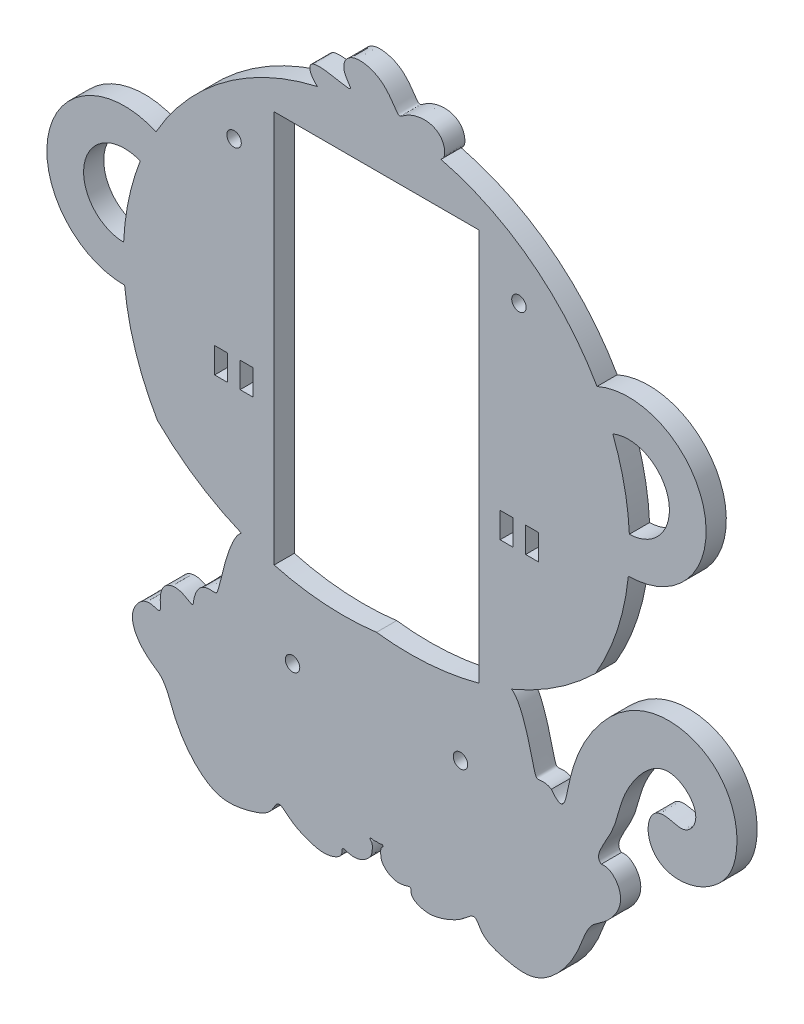
SolidWorks part; units mm, degrees
ref_plane "Front Plane" through (0, 0, 0) normal (0, 0, 1) x (1, 0, 0)
ref_plane "Top Plane" through (0, 0, 0) normal (0, 1, 0) x (1, 0, 0)
ref_plane "Right Plane" through (0, 0, 0) normal (1, 0, 0) x (0, 0, -1)
sketch "Model" plane through (0, 0, 0) normal (0, 0, 1) x (1, 0, 0)
  line L0 (-354.7776, 349.4226) -> (-354.7776, 392.0292) construction
  line L1 (-368.5276, 390.0292) -> (-368.5276, 362.0292)
  line L2 (-368.5276, 390.0292) -> (-341.0276, 390.0292)
  line L21 (-354.7776, 390.0292) -> (-354.7776, 362.0292)
  line L26 (-368.5276, 362.0292) -> (-341.0276, 362.0292)
  line L27 (-341.0276, 390.0292) -> (-341.0276, 362.0292)
  line L28 (-354.7776, 390.0292) -> (-354.7776, 497.7106) construction
  line L29 (-368.5276, 390.0292) -> (-378.8528, 390.0292)
  line L31 (-368.5276, 486.0185) -> (-378.8528, 486.0185)
  line L32 (-378.8528, 390.0292) -> (-378.8528, 486.0185)
  line L33 (-378.8528, 412.6938) -> (-394.4933, 412.6938)
  line L34 (-378.8528, 412.6938) -> (-378.8528, 468.4071)
  line L35 (-378.8528, 468.4071) -> (-394.4933, 468.4071)
  line L36 (-394.4933, 412.6938) -> (-394.4933, 468.4071)
  line L37 (-354.7776, 390.0292) -> (-368.5276, 390.0292)
  line L38 (-354.7776, 390.0292) -> (-354.7776, 486.0185)
  line L39 (-354.7776, 486.0185) -> (-368.5276, 486.0185)
  line L41 (-354.7776, 486.0185) -> (-341.0276, 486.0185)
  line L42 (-341.0276, 486.0185) -> (-330.7024, 486.0185)
  line L43 (-341.0276, 390.0292) -> (-330.7024, 390.0292)
  line L44 (-330.7024, 412.6938) -> (-315.0619, 412.6938)
  line L45 (-315.0619, 412.6938) -> (-315.0619, 468.4071)
  line L46 (-330.7024, 468.4071) -> (-315.0619, 468.4071)
  line L47 (-330.7024, 390.0292) -> (-330.7024, 486.0185)
  line L56 (-325.7024, 431.4116) -> (-322.7024, 431.4116)
  line L57 (-325.7024, 431.4116) -> (-325.7024, 425.4116)
  line L58 (-325.7024, 425.4116) -> (-322.7024, 425.4116)
  line L59 (-322.7024, 431.4116) -> (-322.7024, 425.4116)
  line L61 (-319.7024, 431.4116) -> (-316.7024, 431.4116)
  line L62 (-319.7024, 431.4116) -> (-319.7024, 425.4116)
  line L63 (-319.7024, 425.4116) -> (-316.7024, 425.4116)
  line L64 (-316.7024, 431.4116) -> (-316.7024, 425.4116)
  line L65 (-389.8528, 425.4116) -> (-392.8528, 425.4116)
  line L66 (-392.8528, 431.4116) -> (-392.8528, 425.4116)
  line L67 (-389.8528, 431.4116) -> (-392.8528, 431.4116)
  line L68 (-389.8528, 431.4116) -> (-389.8528, 425.4116)
  line L69 (-383.8528, 425.4116) -> (-386.8528, 425.4116)
  line L70 (-386.8528, 431.4116) -> (-386.8528, 425.4116)
  line L71 (-383.8528, 431.4116) -> (-386.8528, 431.4116)
  line L72 (-383.8528, 431.4116) -> (-383.8528, 425.4116)
  line L75 (-341.0276, 486.0185) -> (-354.7776, 486.0185)
  circle A0 centre (-295.506, 451.3512) radius 18.2563
  circle A1 centre (-295.506, 451.3512) radius 9.6191
  circle A2 centre (-414.0491, 451.3512) radius 9.6191
  circle A3 centre (-414.0491, 451.3512) radius 18.2562
  arc A4 (-354.7776, 392.0292) -> (-303.2483, 409.4214) centre (-346.9752, 453.9435) ccw
  arc A5 (-303.2483, 409.4214) -> (-354.7776, 497.7106) centre (-353.9365, 439.0196) ccw
  arc A6 (-354.7776, 497.7106) -> (-406.3069, 409.4214) centre (-355.6187, 439.0196) ccw
  arc A7 (-406.3069, 409.4214) -> (-354.7776, 392.0292) centre (-362.58, 453.9435) ccw
  circle A8 centre (-388.2776, 475.7792) radius 1.7 construction
  circle A9 centre (-321.2776, 475.7792) radius 1.7 construction
  circle A10 centre (-388.2776, 475.7792) radius 1.7
  circle A11 centre (-321.2776, 475.7792) radius 1.7
  circle A12 centre (-374.5276, 375.7792) radius 1.7 construction
  circle A13 centre (-335.0276, 375.7792) radius 1.7 construction
  circle A14 centre (-374.5276, 375.7792) radius 1.7
  circle A15 centre (-335.0276, 375.7792) radius 1.7
  spline S0 degree 5 poles (-386.5513, 396.3273) (-386.9161, 396.0792) (-387.366, 395.6344) (-387.8968, 394.8986) (-388.5033, 393.7572) (-389.1715, 392.131) (-389.5779, 391.0147) (-389.9703, 389.8193) (-390.4193, 388.3234) (-390.8333, 386.8049) (-391.2016, 385.3464) (-391.5167, 384.0353) (-391.7817, 382.9443) (-391.9754, 382.2094) (-392.154, 381.6648) (-392.3367, 381.3111) (-392.5515, 381.1299) (-392.8335, 381.0822) (-393.2115, 381.1155) (-393.6934, 381.1695) (-394.2612, 381.1826) (-394.881, 381.0994) (-395.5104, 380.8776) (-396.1059, 380.4945) (-396.6315, 379.9559) (-397.064, 379.2975) (-397.3921, 378.574) (-397.6173, 377.8496) (-397.7535, 377.1888) (-397.8274, 376.647) (-397.8791, 376.2603) (-397.9596, 376.0385) (-398.1148, 375.9725) (-398.366, 376.0408) (-398.7069, 376.2147) (-399.1201, 376.4601) (-399.5915, 376.7412) (-400.118, 377.0223) (-400.6998, 377.2689) (-401.4638, 377.484) (-402.3002, 377.5538) (-403.1741, 377.4267) (-404.0022, 377.0659) (-404.6982, 376.4644) (-405.1535, 375.8118) (-405.4613, 375.0322) (-405.6199, 374.1669) (-405.658, 373.2789) (-405.6265, 372.4425) (-405.5875, 371.7311) (-405.6037, 371.2053) (-405.7274, 370.9008) (-405.9901, 370.8167) (-406.3911, 370.9021) (-406.9056, 371.0748) (-407.4962, 371.2433) (-408.1222, 371.3275) (-408.7511, 371.2827) (-409.3596, 371.0975) (-409.9312, 370.7828) (-410.4544, 370.3635) (-410.9212, 369.8697) (-411.3251, 369.3269) (-411.6596, 368.7503) (-411.9191, 368.1478) (-412.0987, 367.5224) (-412.1944, 366.8744) (-412.2033, 366.204) (-412.0922, 365.2374) (-411.7958, 364.2405) (-411.2536, 363.0979) (-410.5055, 362.004) (-409.6286, 361.0209) (-408.9407, 360.363) (-408.2617, 359.7955) (-407.7193, 359.3836) (-407.2138, 359.0282) (-406.7532, 358.7179) (-406.3372, 358.4326) (-405.9584, 358.1461) (-405.6064, 357.8322) (-405.2709, 357.469) (-404.9452, 357.0452) (-404.6288, 356.5637) (-404.3252, 356.0366) (-404.0394, 355.4808) (-403.7755, 354.9137) (-403.4863, 354.2349) (-403.2244, 353.5638) (-402.972, 352.8931) (-402.7045, 352.203) (-402.4017, 351.478) (-402.0626, 350.7211) (-401.6746, 349.928) (-401.239, 349.111) (-400.7631, 348.2898) (-400.2543, 347.482) (-399.7226, 346.693) (-399.1634, 345.9321) (-398.5743, 345.1992) (-397.9495, 344.4888) (-397.2819, 343.7971) (-396.6937, 343.2329) (-395.9467, 342.5739) (-395.1459, 341.9478) (-394.2909, 341.3752) (-393.3842, 340.8821) (-392.43, 340.4917) (-391.606, 340.244) (-390.756, 340.0794) (-389.8831, 339.9983) (-388.9906, 339.995) (-388.0822, 340.0607) (-387.1626, 340.184) (-386.2377, 340.3533) (-385.315, 340.5579) (-384.404, 340.7898) (-383.5163, 341.0454) (-382.6665, 341.327) (-381.8713, 341.6429) (-381.1468, 342.0028) (-380.5061, 342.4143) (-379.9577, 342.8796) (-379.5022, 343.3918) (-379.1308, 343.9312) (-378.8219, 344.461) (-378.5447, 344.9321) (-378.2678, 345.2959) (-377.9655, 345.5144) (-377.6259, 345.571) (-377.2571, 345.4813) (-376.8758, 345.2788) (-376.4963, 345.0025) (-376.1171, 344.6823) (-375.7208, 344.3352) (-375.2832, 343.9706) (-374.7791, 343.5936) (-374.1903, 343.2075) (-373.3777, 342.7411) (-372.4498, 342.2849) (-371.4489, 341.8618) (-370.4344, 341.4969) (-369.4571, 341.2116) (-368.6859, 341.0352) (-367.9644, 340.9249) (-367.2855, 340.8811) (-366.6359, 340.9021) (-366.0015, 340.9842) (-365.3739, 341.1239) (-364.7563, 341.3185) (-364.1709, 341.5681) (-363.6579, 341.8743) (-363.2584, 342.2351) (-362.9996, 342.6398) (-362.8828, 343.0653) (-362.8624, 343.4679) (-362.8603, 343.7943) (-362.8008, 344.002) (-362.6453, 344.0822) (-362.4039, 344.0645) (-362.091, 343.9838) (-361.7122, 343.8689) (-361.2711, 343.747) (-360.7722, 343.6434) (-360.2251, 343.5846) (-359.6439, 343.594) (-359.0456, 343.6889) (-358.3311, 343.9146) (-357.653, 344.2718) (-357.0557, 344.716) (-356.5775, 345.1787) (-356.2334, 345.621) (-356.0331, 345.9754) (-355.9027, 346.3429) (-355.8208, 346.7573) (-355.7698, 347.2366) (-355.7451, 347.7596) (-355.7624, 348.2488) (-355.8386, 348.6234) (-355.9777, 348.8376) (-356.1508, 348.9418) (-356.2927, 349.0757) (-356.3365, 349.2881) (-356.2363, 349.4431) (-355.9971, 349.4554) (-355.6775, 349.3823) (-355.3456, 349.3188) (-355.1001, 349.3199) (-354.9324, 349.357) (-354.828, 349.398) (-354.7776, 349.4226) knots 0 0 0 0 0 0 0.02 0.025 0.03 0.035 0.04 0.045 0.05 0.06 0.065 0.07 0.075 0.08 0.085 0.09 0.095 0.1 0.105 0.11 0.115 0.12 0.125 0.13 0.135 0.14 0.145 0.15 0.155 0.16 0.165 0.17 0.175 0.18 0.185 0.19 0.195 0.2 0.205 0.21 0.22 0.225 0.23 0.235 0.24 0.245 0.25 0.255 0.26 0.265 0.27 0.275 0.28 0.285 0.29 0.295 0.3 0.305 0.31 0.315 0.32 0.325 0.33 0.335 0.34 0.345 0.35 0.355 0.36 0.375 0.38 0.39 0.395 0.4 0.405 0.41 0.415 0.42 0.425 0.43 0.435 0.44 0.445 0.45 0.455 0.46 0.465 0.47 0.48 0.485 0.49 0.495 0.5 0.51 0.515 0.52 0.525 0.53 0.54 0.545 0.55 0.555 0.56 0.565 0.575 0.58 0.585 0.59 0.595 0.6 0.605 0.61 0.615 0.62 0.625 0.63 0.635 0.64 0.645 0.65 0.655 0.66 0.665 0.67 0.675 0.68 0.685 0.69 0.695 0.7 0.705 0.71 0.715 0.72 0.725 0.73 0.735 0.74 0.745 0.755 0.76 0.765 0.77 0.775 0.78 0.785 0.79 0.795 0.8 0.805 0.81 0.815 0.82 0.825 0.83 0.835 0.84 0.845 0.85 0.855 0.86 0.865 0.87 0.875 0.88 0.885 0.89 0.895 0.905 0.91 0.915 0.92 0.925 0.93 0.935 0.94 0.945 0.95 0.955 0.96 0.965 0.97 0.975 0.98 0.985 0.99 0.995 1 1 1 1 1 1 weights 1 1 1 1 1 1 1 1 1 1 1 1 1 1 1 1 1 1 1 1 1 1 1 1 1 1 1 1 1 1 1 1 1 1 1 1 1 1 1 1 1 1 1 1 1 1 1 1 1 1 1 1 1 1 1 1 1 1 1 1 1 1 1 1 1 1 1 1 1 1 1 1 1 1 1 1 1 1 1 1 1 1 1 1 1 1 1 1 1 1 1 1 1 1 1 1 1 1 1 1 1 1 1 1 1 1 1 1 1 1 1 1 1 1 1 1 1 1 1 1 1 1 1 1 1 1 1 1 1 1 1 1 1 1 1 1 1 1 1 1 1 1 1 1 1 1 1 1 1 1 1 1 1 1 1 1 1 1 1 1 1 1 1 1 1 1 1 1 1 1 1 1 1 1 1 1 1 1 1 1 1 1 1 1 1 1 1 1 1 1 1
  spline S1 degree 5 poles (-323.0039, 396.3273) (-322.6391, 396.0792) (-322.1892, 395.6344) (-321.6584, 394.8986) (-321.0519, 393.7572) (-320.3837, 392.131) (-319.9773, 391.0147) (-319.5849, 389.8193) (-319.1359, 388.3234) (-318.7219, 386.8049) (-318.3536, 385.3464) (-318.0385, 384.0353) (-317.7735, 382.9443) (-317.5798, 382.2094) (-317.4012, 381.6648) (-317.2185, 381.3111) (-317.0037, 381.1299) (-316.7217, 381.0822) (-316.3437, 381.1155) (-315.8618, 381.1695) (-315.294, 381.1826) (-314.6741, 381.0994) (-314.0448, 380.8776) (-313.4493, 380.4945) (-312.9237, 379.9559) (-312.4912, 379.2975) (-312.1631, 378.574) (-311.9379, 377.8496) (-311.8017, 377.1888) (-311.7278, 376.647) (-311.6761, 376.2603) (-311.5956, 376.0385) (-311.4404, 375.9725) (-311.1892, 376.0408) (-310.8483, 376.2147) (-310.4351, 376.4601) (-309.9637, 376.7412) (-309.4372, 377.0223) (-308.8554, 377.2689) (-308.0914, 377.484) (-307.2549, 377.5538) (-306.3811, 377.4267) (-305.553, 377.0659) (-304.857, 376.4644) (-304.4017, 375.8118) (-304.0939, 375.0322) (-303.9353, 374.1669) (-303.8972, 373.2789) (-303.9287, 372.4425) (-303.9677, 371.7311) (-303.9515, 371.2053) (-303.8278, 370.9008) (-303.5651, 370.8167) (-303.1641, 370.9021) (-302.6496, 371.0748) (-302.0589, 371.2433) (-301.433, 371.3275) (-300.8041, 371.2827) (-300.1956, 371.0975) (-299.624, 370.7828) (-299.1008, 370.3635) (-298.634, 369.8697) (-298.2301, 369.3269) (-297.8956, 368.7503) (-297.6361, 368.1478) (-297.4565, 367.5224) (-297.3608, 366.8744) (-297.3519, 366.204) (-297.463, 365.2374) (-297.7594, 364.2405) (-298.3016, 363.0979) (-299.0496, 362.004) (-299.9266, 361.0209) (-300.6145, 360.363) (-301.2935, 359.7955) (-301.8359, 359.3836) (-302.3414, 359.0282) (-302.8019, 358.7179) (-303.218, 358.4326) (-303.5968, 358.1461) (-303.9488, 357.8322) (-304.2843, 357.469) (-304.61, 357.0452) (-304.9264, 356.5637) (-305.23, 356.0366) (-305.5158, 355.4808) (-305.7797, 354.9137) (-306.0689, 354.2349) (-306.3308, 353.5638) (-306.5832, 352.8931) (-306.8507, 352.203) (-307.1535, 351.478) (-307.4926, 350.7211) (-307.8805, 349.928) (-308.3162, 349.111) (-308.7921, 348.2898) (-309.3008, 347.482) (-309.8326, 346.693) (-310.3918, 345.9321) (-310.9809, 345.1992) (-311.6057, 344.4888) (-312.2733, 343.7971) (-312.8615, 343.2329) (-313.6085, 342.5739) (-314.4093, 341.9478) (-315.2643, 341.3752) (-316.171, 340.8821) (-317.1251, 340.4917) (-317.9492, 340.244) (-318.7992, 340.0794) (-319.6721, 339.9983) (-320.5646, 339.995) (-321.473, 340.0607) (-322.3926, 340.184) (-323.3175, 340.3533) (-324.2402, 340.5579) (-325.1512, 340.7898) (-326.0389, 341.0454) (-326.8887, 341.327) (-327.6839, 341.6429) (-328.4084, 342.0028) (-329.049, 342.4143) (-329.5975, 342.8796) (-330.053, 343.3918) (-330.4244, 343.9312) (-330.7333, 344.461) (-331.0105, 344.9321) (-331.2874, 345.2959) (-331.5897, 345.5144) (-331.9293, 345.571) (-332.298, 345.4813) (-332.6794, 345.2788) (-333.0589, 345.0025) (-333.4381, 344.6823) (-333.8343, 344.3352) (-334.272, 343.9706) (-334.7761, 343.5936) (-335.3649, 343.2075) (-336.1775, 342.7411) (-337.1053, 342.2849) (-338.1063, 341.8618) (-339.1207, 341.4969) (-340.0981, 341.2116) (-340.8693, 341.0352) (-341.5908, 340.9249) (-342.2697, 340.8811) (-342.9193, 340.9021) (-343.5537, 340.9842) (-344.1813, 341.1239) (-344.7989, 341.3185) (-345.3842, 341.5681) (-345.8972, 341.8743) (-346.2968, 342.2351) (-346.5556, 342.6398) (-346.6724, 343.0653) (-346.6928, 343.4679) (-346.6949, 343.7943) (-346.7544, 344.002) (-346.9099, 344.0822) (-347.1513, 344.0645) (-347.4642, 343.9838) (-347.843, 343.8689) (-348.2841, 343.747) (-348.783, 343.6434) (-349.33, 343.5846) (-349.9113, 343.594) (-350.5096, 343.6889) (-351.2241, 343.9146) (-351.9022, 344.2718) (-352.4995, 344.716) (-352.9777, 345.1787) (-353.3218, 345.621) (-353.5221, 345.9754) (-353.6525, 346.3429) (-353.7344, 346.7573) (-353.7854, 347.2366) (-353.8101, 347.7596) (-353.7928, 348.2488) (-353.7166, 348.6234) (-353.5775, 348.8376) (-353.4043, 348.9418) (-353.2625, 349.0757) (-353.2187, 349.2881) (-353.3188, 349.4431) (-353.5581, 349.4554) (-353.8776, 349.3823) (-354.2096, 349.3188) (-354.4551, 349.3199) (-354.6228, 349.357) (-354.7272, 349.398) (-354.7776, 349.4226) knots 0 0 0 0 0 0 0.02 0.025 0.03 0.035 0.04 0.045 0.05 0.06 0.065 0.07 0.075 0.08 0.085 0.09 0.095 0.1 0.105 0.11 0.115 0.12 0.125 0.13 0.135 0.14 0.145 0.15 0.155 0.16 0.165 0.17 0.175 0.18 0.185 0.19 0.195 0.2 0.205 0.21 0.22 0.225 0.23 0.235 0.24 0.245 0.25 0.255 0.26 0.265 0.27 0.275 0.28 0.285 0.29 0.295 0.3 0.305 0.31 0.315 0.32 0.325 0.33 0.335 0.34 0.345 0.35 0.355 0.36 0.375 0.38 0.39 0.395 0.4 0.405 0.41 0.415 0.42 0.425 0.43 0.435 0.44 0.445 0.45 0.455 0.46 0.465 0.47 0.48 0.485 0.49 0.495 0.5 0.51 0.515 0.52 0.525 0.53 0.54 0.545 0.55 0.555 0.56 0.565 0.575 0.58 0.585 0.59 0.595 0.6 0.605 0.61 0.615 0.62 0.625 0.63 0.635 0.64 0.645 0.65 0.655 0.66 0.665 0.67 0.675 0.68 0.685 0.69 0.695 0.7 0.705 0.71 0.715 0.72 0.725 0.73 0.735 0.74 0.745 0.755 0.76 0.765 0.77 0.775 0.78 0.785 0.79 0.795 0.8 0.805 0.81 0.815 0.82 0.825 0.83 0.835 0.84 0.845 0.85 0.855 0.86 0.865 0.87 0.875 0.88 0.885 0.89 0.895 0.905 0.91 0.915 0.92 0.925 0.93 0.935 0.94 0.945 0.95 0.955 0.96 0.965 0.97 0.975 0.98 0.985 0.99 0.995 1 1 1 1 1 1 weights 1 1 1 1 1 1 1 1 1 1 1 1 1 1 1 1 1 1 1 1 1 1 1 1 1 1 1 1 1 1 1 1 1 1 1 1 1 1 1 1 1 1 1 1 1 1 1 1 1 1 1 1 1 1 1 1 1 1 1 1 1 1 1 1 1 1 1 1 1 1 1 1 1 1 1 1 1 1 1 1 1 1 1 1 1 1 1 1 1 1 1 1 1 1 1 1 1 1 1 1 1 1 1 1 1 1 1 1 1 1 1 1 1 1 1 1 1 1 1 1 1 1 1 1 1 1 1 1 1 1 1 1 1 1 1 1 1 1 1 1 1 1 1 1 1 1 1 1 1 1 1 1 1 1 1 1 1 1 1 1 1 1 1 1 1 1 1 1 1 1 1 1 1 1 1 1 1 1 1 1 1 1 1 1 1 1 1 1 1 1 1
  spline S2 degree 5 poles (-313.6608, 380.6036) (-313.4447, 380.3201) (-313.0302, 379.8091) (-312.4617, 379.2104) (-311.8099, 378.7481) (-311.1658, 378.7209) (-310.6734, 379.2168) (-310.2927, 380.1782) (-309.9686, 381.5239) (-309.6406, 383.1622) (-309.2509, 385.0015) (-308.7553, 386.9633) (-308.0017, 389.3938) (-307.0301, 391.8531) (-305.8363, 394.2764) (-304.438, 396.6235) (-302.856, 398.8596) (-301.4232, 400.6299) (-299.5708, 402.6142) (-297.5538, 404.3848) (-295.3743, 405.8881) (-292.6508, 407.2693) (-289.33, 408.2696) (-286.299, 408.5941) (-283.2651, 408.3445) (-280.3791, 407.5391) (-278.0928, 406.4785) (-276.3489, 405.3668) (-274.4851, 403.7878) (-272.9371, 401.946) (-271.7278, 399.9069) (-270.8571, 397.7451) (-270.3065, 395.5388) (-270.0462, 393.71) (-269.965, 391.9301) (-270.041, 390.2346) (-270.2523, 388.6524) (-270.5799, 387.2019) (-271.0097, 385.8888) (-271.5359, 384.701) (-272.1612, 383.6109) (-272.8958, 382.5869) (-273.7555, 381.6014) (-274.7609, 380.6417) (-275.9355, 379.7174) (-277.2973, 378.8569) (-278.8515, 378.1044) (-280.5823, 377.5164) (-282.4459, 377.1586) (-284.3607, 377.1036) (-286.2191, 377.417) (-287.9032, 378.1427) (-289.299, 379.2867) (-290.311, 380.8037) (-290.8776, 382.5789) (-290.9832, 384.4209) (-290.6506, 386.112) (-289.936, 387.4514) (-288.9223, 388.2997) (-287.7148, 388.6275) (-286.4328, 388.5495) (-285.1876, 388.2576) (-284.0619, 387.9667) (-283.0865, 387.8525) (-282.2242, 388) (-281.4248, 388.4326) (-280.673, 389.1343) (-280.0427, 390.0762) (-279.6515, 391.2145) (-279.6146, 392.4895) (-279.9934, 393.8227) (-280.764, 395.118) (-281.8511, 396.2738) (-283.152, 397.1938) (-284.5629, 397.798) (-286.0086, 398.0348) (-287.4505, 397.8849) (-288.8706, 397.3556) (-290.2614, 396.4772) (-291.6143, 395.2987) (-292.9061, 393.8845) (-294.101, 392.3076) (-295.162, 390.6429) (-296.0582, 388.9596) (-296.775, 387.314) (-297.3214, 385.7431) (-297.7428, 384.2552) (-298.1147, 382.8324) (-298.5188, 381.4451) (-299.0233, 380.0639) (-299.6638, 378.6704) (-300.4174, 377.2729) (-301.2032, 375.907) (-301.9108, 374.6227) (-302.4229, 373.4731) (-302.6383, 372.5046) (-302.5279, 371.8953) (-302.2784, 371.535) (-302.0378, 371.3378) (-301.8989, 371.25) knots 0 0 0 0 0 0 0.01 0.02 0.03 0.04 0.05 0.06 0.07 0.08 0.09 0.1 0.11 0.13 0.14 0.15 0.16 0.17 0.18 0.2 0.21 0.22 0.24 0.26 0.27 0.28 0.29 0.3 0.31 0.33 0.34 0.35 0.36 0.37 0.38 0.39 0.4 0.41 0.42 0.43 0.44 0.45 0.46 0.47 0.48 0.49 0.5 0.51 0.52 0.53 0.54 0.55 0.56 0.57 0.58 0.59 0.6 0.61 0.62 0.63 0.64 0.65 0.66 0.67 0.68 0.69 0.7 0.71 0.72 0.73 0.74 0.75 0.76 0.77 0.78 0.79 0.8 0.81 0.82 0.83 0.84 0.85 0.86 0.87 0.88 0.89 0.9 0.91 0.92 0.93 0.94 0.95 0.96 0.97 0.98 0.99 1 1 1 1 1 1 weights 1 1 1 1 1 1 1 1 1 1 1 1 1 1 1 1 1 1 1 1 1 1 1 1 1 1 1 1 1 1 1 1 1 1 1 1 1 1 1 1 1 1 1 1 1 1 1 1 1 1 1 1 1 1 1 1 1 1 1 1 1 1 1 1 1 1 1 1 1 1 1 1 1 1 1 1 1 1 1 1 1 1 1 1 1 1 1 1 1 1 1 1 1 1 1 1 1 1 1 1
  spline S3 degree 5 poles (-368.6485, 496.2522) (-368.7445, 496.3189) (-368.9332, 496.4614) (-369.2068, 496.7025) (-369.5526, 497.079) (-369.9454, 497.6352) (-370.274, 498.2589) (-370.4903, 498.915) (-370.5107, 499.5416) (-370.2384, 500.0643) (-369.5991, 500.4175) (-368.5716, 500.5624) (-367.2236, 500.5088) (-365.6871, 500.3043) (-364.1304, 500.0214) (-362.7304, 499.745) (-361.6458, 499.5606) (-360.9878, 499.5411) (-360.7964, 499.7361) (-361.0037, 500.1558) (-361.4562, 500.7754) (-361.9696, 501.5464) (-362.3683, 502.407) (-362.5408, 503.2925) (-362.4544, 504.1433) (-362.127, 504.907) (-361.609, 505.5429) (-360.9624, 506.0248) (-360.2377, 506.3463) (-359.4651, 506.519) (-358.6621, 506.5638) (-357.8368, 506.5034) (-356.9934, 506.3554) (-356.1367, 506.1232) (-355.2752, 505.7947) (-354.4199, 505.3529) (-353.5839, 504.7839) (-352.7824, 504.0858) (-352.0321, 503.2767) (-351.3511, 502.4053) (-350.7568, 501.5504) (-350.2591, 500.8009) (-349.8549, 500.2405) (-349.5224, 499.9306) (-349.215, 499.8941) (-348.8555, 500.0985) (-348.3621, 500.4755) (-347.6717, 500.9383) (-346.77, 501.4022) (-345.6888, 501.7923) (-344.4899, 502.0451) (-343.2539, 502.1125) (-342.0666, 501.9648) (-341.0067, 501.594) (-340.1326, 501.0174) (-339.4704, 500.2805) (-339.0219, 499.4471) (-338.7725, 498.5899) (-338.6988, 497.7804) (-338.776, 497.0807) (-338.9866, 496.5313) (-339.2553, 496.2274) (-339.5119, 496.0787) (-339.7073, 496.0148) (-339.8111, 495.9917) knots 0 0 0 0 0 0 0.016667 0.033333 0.05 0.066667 0.083333 0.1 0.116667 0.133333 0.15 0.166667 0.183333 0.2 0.216667 0.233333 0.25 0.266667 0.283333 0.3 0.316667 0.333333 0.35 0.366667 0.383333 0.4 0.416667 0.433333 0.45 0.466667 0.483333 0.5 0.516667 0.533333 0.55 0.566667 0.583333 0.6 0.616667 0.633333 0.65 0.666667 0.683333 0.7 0.716667 0.733333 0.75 0.766667 0.783333 0.8 0.816667 0.833333 0.85 0.866667 0.883333 0.9 0.916667 0.933333 0.95 0.966667 0.983333 1 1 1 1 1 1 weights 1 1 1 1 1 1 1 1 1 1 1 1 1 1 1 1 1 1 1 1 1 1 1 1 1 1 1 1 1 1 1 1 1 1 1 1 1 1 1 1 1 1 1 1 1 1 1 1 1 1 1 1 1 1 1 1 1 1 1 1 1 1 1 1 1
  dimension "D2" = 13.75
  dimension "D3" = 2
  dimension "D1" = 28
  dimension "D4" = 3
  dimension "D5" = 6
  dimension "D6" = 5
  dimension "D7" = 3
extrude "Boss-Extrude1" add sketch "Model" along normal blind 4.75 contours A6 A7 A4 A5 A0 A3 | A3 A6 A2 | A2 A6 | A6 A3 A2 | A1 A5 A0 | A1 A5 | A5 A1 A0 | S2 S1 A4 L47 L43 L27 L26 L1 L29 L32 A7 S0 | S2 S1 | S3 A6 A5 | L47 L44 L45 L46 | L36 L33 L32 L34 L35 | A4 L38 L2 L43 L47 | A7 L32 L29 L2 L38 | L1 L26 L21 L2 | L27 L2 L21 L26 region at (-361.6526, 376.0292, 0) region at (-368.4394, 391.1384, 0) region at (-369.8065, 376.0292, 0) region at (-341.1158, 391.1384, 0) region at (-347.9026, 376.0292, 0) region at (-382.2354, 396.3794, 0) region at (-386.6007, 441.0735, 0) region at (-322.9545, 441.0735, 0) region at (-404.0204, 449.2347, 0) region at (-431.4752, 455.029, 0) region at (-305.971, 377.819, 0) region at (-294.8154, 437.3981, 0) region at (-305.5348, 449.2347, 0) region at (-409.3752, 450.3648, 0) region at (-300.18, 450.3648, 0) region at (-354.5371, 500.3437, 0)
